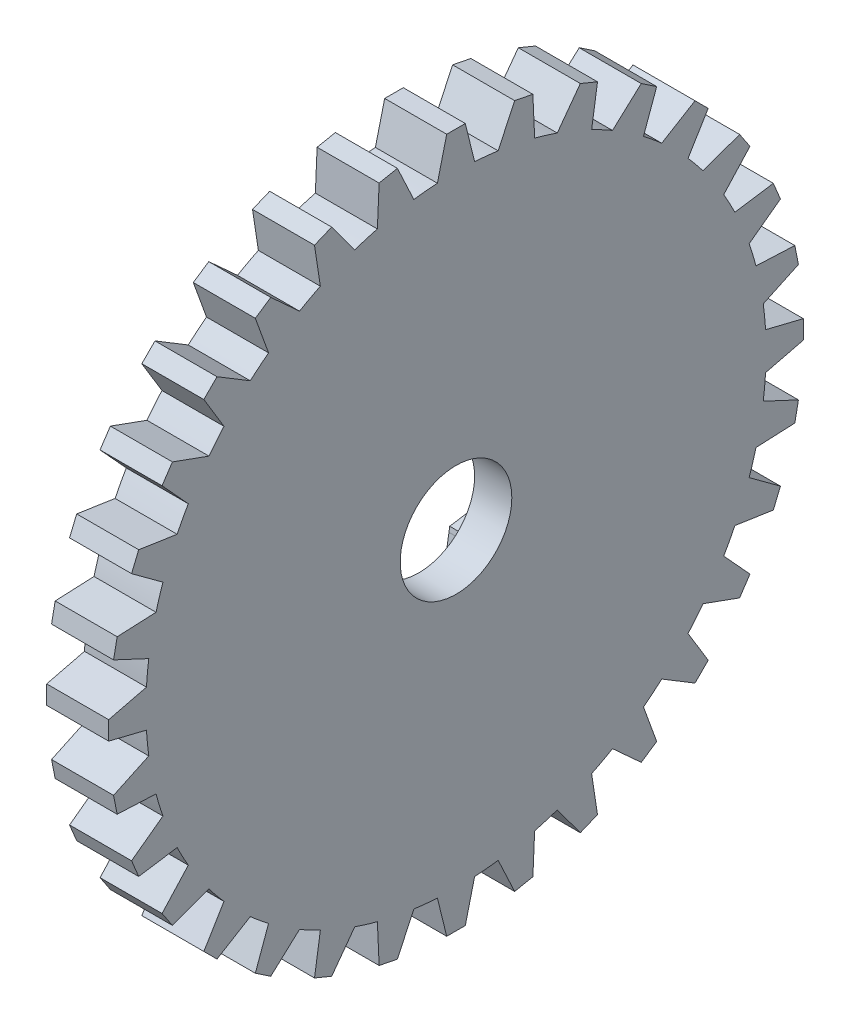
SolidWorks part; units mm, degrees
ref_plane "Front" through (0, 0, 0) normal (0, 0, 1) x (1, 0, 0)
ref_plane "Top" through (0, 0, 0) normal (0, 1, 0) x (1, 0, 0)
ref_plane "Right" through (0, 0, 0) normal (1, 0, 0) x (0, 0, -1)
sketch "Sketch1" plane through (0, 0, 0) normal (1, 0, 0) x (0, 0, -1)
  circle A0 centre (0, 0) radius 25
  dimension "D1" = 50
extrude "Boss-Extrude1" add sketch "Sketch1" along normal blind 5
sketch "Sketch3" plane through (5, 0, 0) normal (1, 0, 0) x (0, 0, -1)
  line L0 (0, 25) -> (0, 28) construction
  line L1 (0.75, 28) -> (-0.75, 28)
  line L2 (-0.75, 28) -> (-1.5, 24.955)
  line L5 (0.75, 28) -> (1.5, 24.955)
  line L6 (-1.5, 24.955) -> (1.5, 24.955)
  circle A0 centre (0, 0) radius 25 construction
  dimension "D1" = 3
  dimension "D2" = 1.5
  dimension "D3" = 3
extrude "Boss-Extrude2" add sketch "Sketch3" against normal up to surface (5 mm away) up to face at (0, 0, -25)
sketch "Sketch4" plane through (0, 0, 0) normal (0, 1, 0) x (1, 0, 0)
  line L0 (0, 0) -> (20, 0) construction
  dimension "D1" = 20
pattern_circular "CirPattern1" count 32 over 360 about axis through (0, 0, 0) along (1, 0, 0) of "Boss-Extrude2"
sketch "Sketch5" plane through (5, 0, 0) normal (1, 0, 0) x (0, 0, -1)
  circle A0 centre (0, 0) radius 4.5
  dimension "D1" = 9
extrude "Cut-Extrude1" cut sketch "Sketch5" against normal up to next
sketch "Sketch6" plane through (0, 0, 0) normal (-1, 0, 0) x (0, 0, 1)
  line L0 (0, 0) -> (0, 4.5) construction
  line L1 (0, 0) -> (3.182, 3.182) construction
  circle A0 centre (0, 16) radius 0.75
  circle A1 centre (-16, 0) radius 0.75
  circle A2 centre (0, 0) radius 4.5 construction
  circle A3 centre (0, -16) radius 0.75
  circle A4 centre (16, 0) radius 0.75
  dimension "D3" = 1.5
  dimension "D1" = 16
  dimension "D2" = 16
  dimension "D4" = 45
extrude "Cut-Extrude2" cut sketch "Sketch6" against normal offset from surface (4 mm away) 1 up to face at (5, 0, -4.5)
sketch "Sketch7" plane through (0, 0, 0) normal (-1, 0, 0) x (0, 0, 1)
  line L0 (-2.5, 17) -> (-4.43, 4.8841)
  line L1 (0, 17) -> (0, 0) construction
  line L2 (2.5, 17) -> (4.43, 4.8841)
  line L3 (17, 2.5) -> (4.4914, 4.4926)
  line L4 (17, -2.5) -> (4.8841, -4.43)
  line L5 (2.5, -17) -> (4.43, -4.8841)
  line L6 (-2.5, -17) -> (-4.43, -4.8841)
  line L7 (-17, -2.5) -> (-4.4914, -4.4926)
  line L8 (-17, 2.5) -> (-4.4914, 4.4926)
  line L9 (0, 0) -> (4.43, 4.8841) construction
  line L10 (-4.43, 4.8841) -> (-4.4914, 4.4926)
  line L11 (4.43, 4.8841) -> (4.4914, 4.4926)
  line L12 (0, 0) -> (4.5, 0) construction
  line L13 (4.43, -4.8841) -> (4.4914, -4.4926)
  line L14 (-4.43, -4.8841) -> (-4.4914, -4.4926)
  line L15 (4.8841, -4.43) -> (4.4914, -4.4926)
  arc A0 (2.5, 17) -> (-2.5, 17) centre (0, 17) ccw
  arc A1 (17, -2.5) -> (17, 2.5) centre (17, 0) ccw
  arc A2 (-2.5, -17) -> (2.5, -17) centre (0, -17) ccw
  arc A3 (-17, 2.5) -> (-17, -2.5) centre (-17, 0) ccw
  circle A4 centre (0, 0) radius 4.5 construction
  dimension "D1" = 5
  dimension "D2" = 17
  dimension "D3" = 4.43
  dimension "D5" = 6.5939
  dimension "D4" = 4
extrude "Cut-Extrude3" cut sketch "Sketch7" against normal blind 2
